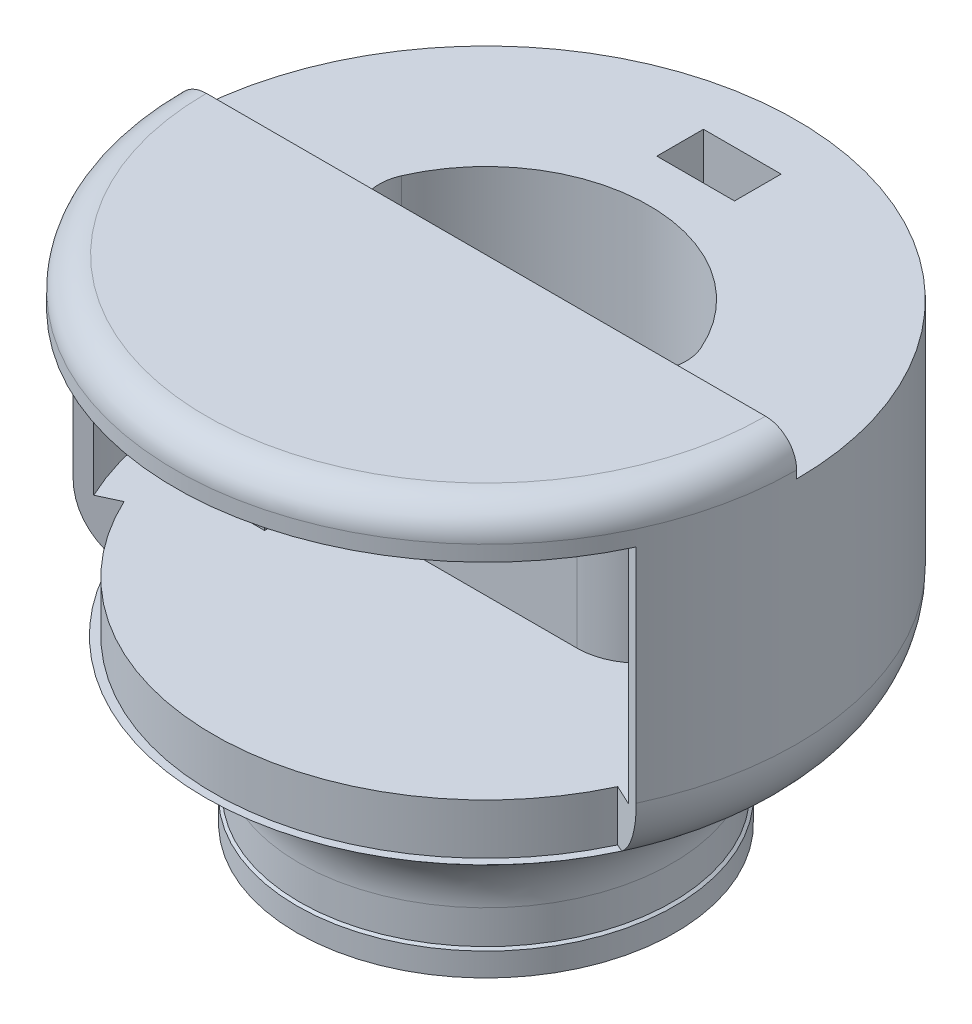
SolidWorks part; units mm, degrees
ref_plane "Front Plane" through (0, 0, 0) normal (0, 0, 1) x (1, 0, 0)
ref_plane "Top Plane" through (0, 0, 0) normal (0, 1, 0) x (1, 0, 0)
ref_plane "Right Plane" through (0, 0, 0) normal (1, 0, 0) x (0, 0, -1)
sketch "Sketch1" plane through (0, 0, 0) normal (0, 0, 1) x (1, 0, 0)
  line L0 (0, 0) -> (0, 90.2242) construction
  line L28 (0, 63.4279) -> (36, 63.4279)
  line L29 (40, 59.4279) -> (40, 28.8468)
  line L30 (22.5, 0) -> (24.35, 0)
  line L31 (24.35, 0) -> (24.35, 3)
  line L32 (24.35, 3) -> (24, 3.25)
  line L33 (24, 3.25) -> (24, 7.5811)
  line L34 (28.5399, 15.9588) -> (35.4601, 20.4691)
  line L35 (0, 13) -> (22, 13)
  line L36 (22.5, 12.5) -> (22.5, 0)
  line L37 (0, 13) -> (0, 63.4279)
  arc A0 (22, 13) -> (22.5, 12.5) centre (22, 12.5) cw
  arc A1 (24, 7.5811) -> (28.5399, 15.9588) centre (34, 7.5811) cw
  arc A2 (35.4601, 20.4691) -> (40, 28.8468) centre (30, 28.8468) ccw
  arc A3 (36, 63.4279) -> (40, 59.4279) centre (36, 59.4279) cw
  point P11 (22.9, 63.4279)
  point P18 (22.5, 13)
  point P21 (24, 13)
  point P24 (40, 23.4279)
  point P27 (40, 63.4279)
  point P28 (28.5604, 23.4279)
  point P31 (22.5, 17)
  dimension "D8" = 9.75
  dimension "D9" = 0.5
  dimension "D4" = 1.85
  dimension "D1" = 22.5
  dimension "D10" = 10
  dimension "D11" = 10
  dimension "D12" = 4
  dimension "D2" = 40
  dimension "D3" = 40
  dimension "D5" = 1.5
  dimension "D6" = 3
  dimension "D7" = 13
revolve "Revolve1" add sketch "Sketch1" angle 360 about L0
ref_plane "Plane1" through (0, 13, 0) normal (0, -1, 0) x (-1, 0, 0)
sketch "Sketch18" plane through (0, 0, 0) normal (0, 0, 1) x (1, 0, 0)
  line L0 (0, 0) -> (0, 101.5813) construction
  line L1 (-24.35, 0) -> (24.35, 0) construction
sketch "Sketch3" plane through (0, 0, 0) normal (0, 0, 1) x (1, 0, 0)
  point P0 (1.2404, 19.1989)
ref_point "Point1"
ref_plane "Plane2" through (0, 0, 22.9) normal (0, 0, 1) x (1, 0, 0)
ref_plane "Plane3" through (0, 0, 40) normal (0, 0, 1) x (1, 0, 0)
ref_plane "Plane4" through (0, 57.4279, 0) normal (0, 1, 0) x (1, 0, 0)
sketch "Sketch9" plane through (0, 57.4279, 0) normal (0, 1, 0) x (1, 0, 0)
  circle A7 centre (0, 0) radius 38
  circle A8 centre (0, 0) radius 40 construction
  circle A9 centre (0, 0) radius 23
  dimension "D1" = 2
  dimension "D2" = 46
ref_plane "Plane5" through (0, 13, 0) normal (0, -1, 0) x (-1, 0, 0)
sketch "Sketch11" plane through (0, 13, 0) normal (0, -1, 0) x (-1, 0, 0)
  line L0 (-21, 0) -> (21, 0)
  arc A1 (-21, 0) -> (21, 0) centre (0, 0) cw
  dimension "D1" = 42
extrude "Cut-Extrude3" cut sketch "Sketch11" against normal blind 60
ref_plane "Plane6" through (0, 0, -40) normal (0, 0, -1) x (-1, 0, 0)
extrude "Cut-Extrude5" cut sketch "Sketch9" against normal blind 30
sketch "Sketch19" plane through (0, 0, 0) normal (1, 0, 0) x (0, 0, -1)
  line L0 (-47.0647, 57.4279) -> (-35.0647, 57.4279)
  line L1 (39.6, 57.4279) -> (-39.6, 57.4279) construction
  line L2 (-35.0647, 57.4279) -> (-35.0647, 20.9279)
  line L3 (-35.0647, 20.9279) -> (-47.0647, 20.9279)
  line L4 (-47.0647, 20.9279) -> (-47.0647, 57.4279)
  dimension "D1" = 12
  dimension "D2" = 36.5
revolve "Cut-Revolve2" cut sketch "Sketch19" angle 65 about L0 other way angle 65
ref_plane "Plane7" through (0, 0, 22.5) normal (0, 0, -1) x (-1, 0, 0)
sketch "Sketch21" plane through (0, 0, 22.5) normal (0, 0, -1) x (-1, 0, 0)
  line L0 (0, 0) -> (0, 101.5813) construction
  line L1 (-1.625, 4) -> (1.625, 4)
  line L2 (-1.625, 4) -> (-1.625, 0)
  line L3 (-1.625, 0) -> (1.625, 0)
  line L4 (1.625, 4) -> (1.625, 0)
  line L5 (-1.625, 4) -> (1.625, 0) construction
  line L6 (-1.625, 0) -> (1.625, 4) construction
  line L7 (-22.5, 0) -> (22.5, 0) construction
  point P0 (0, 2)
  dimension "D1" = 4
  dimension "D2" = 3.25
extrude "Boss-Extrude3" add sketch "Sketch21" along normal blind 1.35
pattern_circular "CirPattern1" count 5 over 360 about axis through (0, 0, 0) along (0, -1, 0) of "Boss-Extrude3"
ref_plane "Plane8" through (0, 20.4691, 0) normal (0, 1, 0) x (1, 0, 0)
sketch "Sketch22" plane through (0, 63.4279, 0) normal (0, 1, 0) x (1, 0, 0)
  line L0 (-40, 0) -> (40, 0)
  arc A0 (-40, 0) -> (40, 0) centre (0, 0) cw
  circle A1 centre (0, 0) radius 40 construction
extrude "Cut-Extrude9" cut sketch "Sketch22" against normal blind 5
sketch "Sketch23" plane through (0, 0, -40) normal (0, 0, -1) x (-1, 0, 0)
  line L0 (0, 0) -> (0, 101.5813) construction
  line L1 (39.6, 57.4279) -> (-39.6, 57.4279) construction
  circle A0 centre (0, 44.1379) radius 10.5
  dimension "D1" = 21
  dimension "D2" = 13.29
extrude "Cut-Extrude10" cut sketch "Sketch23" against normal blind 10
sketch "Sketch24" plane through (0, 58.4279, 0) normal (0, 1, 0) x (1, 0, 0)
  line L1 (-7.5, 34) -> (7.5, 34)
  line L2 (-7.5, 34) -> (-7.5, 26)
  line L3 (-7.5, 26) -> (7.5, 26)
  line L4 (7.5, 34) -> (7.5, 26)
  line L5 (-7.5, 34) -> (7.5, 26) construction
  line L6 (-7.5, 26) -> (7.5, 34) construction
  arc A0 (-39.873, 0) -> (39.873, 0) centre (0, 0) ccw construction
  point P0 (0, 30)
  dimension "D1" = 30
  dimension "D2" = 8
  dimension "D3" = 15
extrude "Boss-Extrude4" add sketch "Sketch24" against normal blind 8
sketch "Sketch26" plane through (0, 58.4279, 0) normal (0, 1, 0) x (1, 0, 0)
  line L1 (-5, 33) -> (5, 33)
  line L2 (-5, 33) -> (-5, 27)
  line L3 (-5, 27) -> (5, 27)
  line L4 (5, 33) -> (5, 27)
  line L5 (-5, 33) -> (5, 27) construction
  line L6 (-5, 27) -> (5, 33) construction
  arc A0 (-39.873, 0) -> (39.873, 0) centre (0, 0) ccw construction
  point P0 (0, 30)
  dimension "D1" = 30
  dimension "D2" = 6
  dimension "D3" = 10
extrude "Cut-Extrude11" cut sketch "Sketch26" against normal blind 10
sketch "Sketch27" plane through (7.5, 0, 0) normal (1, 0, 0) x (0, 0, -1)
  line L0 (34, 50.4279) -> (34, 57.4279) construction
  line L1 (28, 56.4279) -> (32, 56.4279)
  line L2 (28, 56.4279) -> (28, 51.4279)
  line L3 (28, 51.4279) -> (32, 51.4279)
  line L4 (32, 56.4279) -> (32, 51.4279)
  line L5 (28, 56.4279) -> (32, 51.4279) construction
  line L6 (28, 51.4279) -> (32, 56.4279) construction
  line L7 (26, 50.4279) -> (26, 57.4279) construction
  line L8 (26, 50.4279) -> (34, 50.4279) construction
  point P0 (30, 53.9279)
  dimension "D1" = 8
  dimension "D2" = 3.5
  dimension "D3" = 5
  dimension "D4" = 4
extrude "Cut-Extrude12" cut sketch "Sketch27" against normal blind 5
ref_plane "Plane10" through (0, 58.4279, 0) normal (0, 1, 0) x (1, 0, 0)
sketch "Sketch28" plane through (0, 57.4279, 0) normal (0, 1, 0) x (1, 0, 0)
  line L0 (-22.9129, -2) -> (22.9129, -2)
  arc A0 (-22.9129, -2) -> (22.9129, -2) centre (0, 0) ccw
  dimension "D1" = 46
  dimension "D2" = 2
extrude "Cut-Extrude14" cut sketch "Sketch28" against normal blind 30
sketch "Sketch29" plane through (0, 0, 0) normal (0, 0, -1) x (-1, 0, 0)
  line L0 (0, 0) -> (0, 101.5813) construction
  line L1 (36, 63.4279) -> (-36, 63.4279) construction
  circle A0 centre (-30.4162, 60.9279) radius 1
  circle A1 centre (30.4162, 60.9279) radius 1
  circle A2 centre (0, 60.9279) radius 1
  dimension "D1" = 2
  dimension "D2" = 2
  dimension "D3" = 2
  dimension "D4" = 2.5
  dimension "D5" = 2.5
  dimension "D6" = 2.5
  dimension "D7" = 9
  dimension "D8" = 9
extrude "Cut-Extrude15" cut sketch "Sketch29" against normal blind 15
fillet "Fillet1" radius 6 2 edges at (-21, 35.7139, 0) (21, 35.7139, 0)
fillet "Fillet2" radius 8 2 edges at (22.9129, 42.4279, 2) (-22.9129, 42.4279, 2)
sketch "Sketch31" plane through (0, 58.4279, 0) normal (0, 1, 0) x (1, 0, 0)
  line L1 (-3.5, -27) -> (3.5, -27)
  line L2 (-3.5, -27) -> (-3.5, -32)
  line L3 (-3.5, -32) -> (3.5, -32)
  line L4 (3.5, -27) -> (3.5, -32)
  line L5 (-3.5, -27) -> (3.5, -32) construction
  line L6 (-3.5, -32) -> (3.5, -27) construction
  point P0 (0, -29.5)
  dimension "D1" = 7
  dimension "D2" = 5
  dimension "D3" = 29.5
extrude "Boss-Extrude7" add sketch "Sketch31" against normal blind 8
